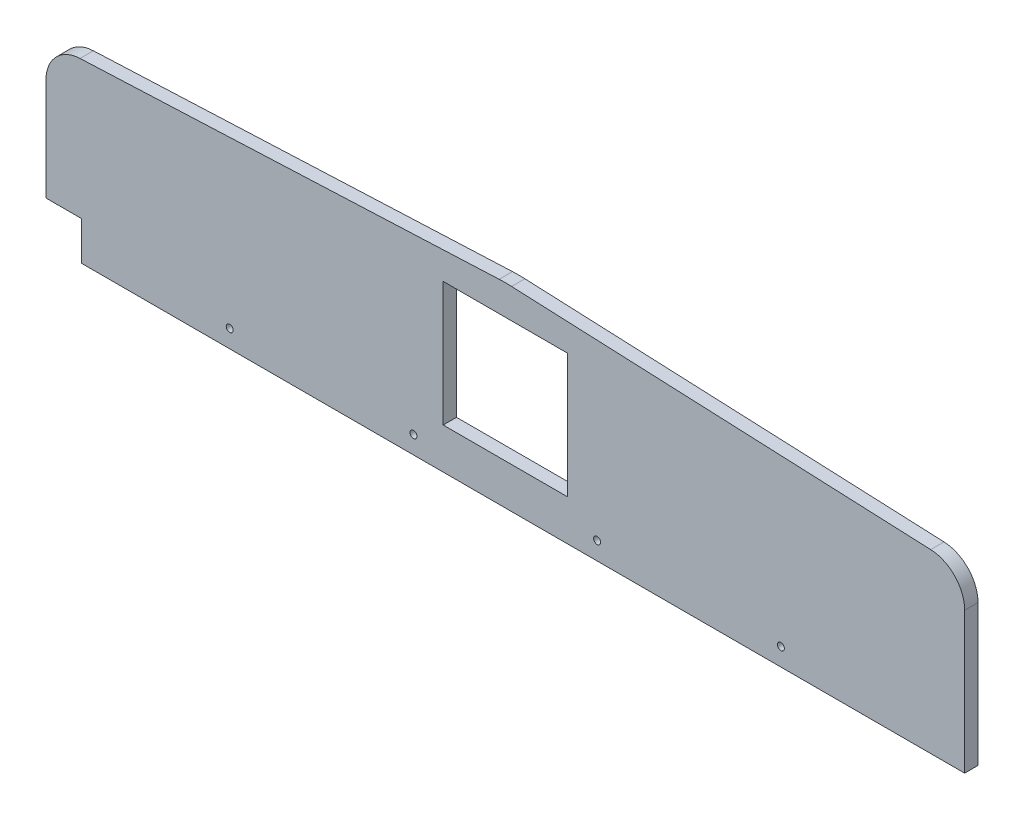
SolidWorks part; units mm, degrees
material "PC High Viscosity"
ref_plane "Front Plane" through (0, 0, 0) normal (0, 0, 1) x (1, 0, 0)
ref_plane "Top Plane" through (0, 0, 0) normal (0, 1, 0) x (1, 0, 0)
ref_plane "Right Plane" through (0, 0, 0) normal (1, 0, 0) x (0, 0, -1)
sketch "Sketch2" plane through (0, 0, 0) normal (0, 0, 1) x (1, 0, 0)
  line L0 (-328.3315, 55.6895) -> (-328.3315, 154.4895)
  line L1 (-328.3315, 154.4895) -> (0, 168.8465)
  line L2 (0, 168.8465) -> (328.2858, 154.4895)
  line L3 (328.2858, 154.4895) -> (328.2858, 55.6895)
  line L4 (328.2858, 55.6895) -> (328.2858, 29.2895)
  line L6 (328.2858, 29.2895) -> (-328.3315, 29.2895)
  line L7 (-328.3315, 29.2895) -> (-328.3315, 55.6895)
  dimension "D1" = 113.157
  dimension "D7" = 328.2858
  dimension "D8" = 98.8
  dimension "D9" = 26.4
extrude "Boss-Extrude1" add sketch "Sketch2" along normal mid plane 9.525
fillet "Fillet1" radius 25.4 2 edges at (328.2858, 154.4895, 0) (-328.3315, 154.4895, 0)
fillet "Fillet2" radius 101.6 1 edges at (0, 168.8465, 0)
sketch "Sketch3" plane through (0, 0, 4.7625) normal (0, 0, 1) x (1, 0, 0)
  line L0 (0, 0) -> (0, 192.0016) construction
  line L1 (-328.3315, 29.2895) -> (-302.9315, 29.2895)
  line L2 (-328.3315, 29.2895) -> (-328.3315, 56.9755)
  line L3 (-328.3315, 56.9755) -> (-302.9315, 56.9755)
  line L4 (-302.9315, 29.2895) -> (-302.9315, 56.9755)
  line L5 (0, 192.0016) -> (0, -60.0751) construction
  dimension "D1" = 25.4
  dimension "D2" = 27.686
extrude "Cut-Extrude1" cut sketch "Sketch3" against normal through all
sketch "Sketch5" plane through (0, 0, 4.7625) normal (0, 0, 1) x (1, 0, 0)
  line L1 (-44.45, 147.336) -> (44.45, 147.336)
  line L2 (-44.45, 147.336) -> (-44.45, 58.436)
  line L3 (-44.45, 58.436) -> (44.45, 58.436)
  line L4 (44.45, 147.336) -> (44.45, 58.436)
  line L5 (-44.45, 147.336) -> (44.45, 58.436) construction
  line L6 (-44.45, 58.436) -> (44.45, 147.336) construction
  point P0 (0, 102.886)
  dimension "D1" = 88.9
  dimension "D2" = 88.9
extrude "Cut-Extrude2" cut sketch "Sketch5" against normal through all
hole_wizard "Tap Drill for M6x1.0 Tap1" positions "Sketch7" profile "Sketch6" hole size "M6x1.0" standard "ANSI Metric" end condition through all
sketch "Sketch7" plane through (0, 0, 4.7625) normal (0, 0, 1) x (1, 0, 0)
  line L0 (-302.9315, 29.2895) -> (328.2858, 29.2895) construction
  line L1 (-328.3315, 130.1759) -> (-328.3315, 56.9755) construction
  point P0 (-197.0135, 41.9895)
  point P2 (-65.6955, 41.9895)
  point P4 (65.6225, 41.9895)
  point P6 (196.9405, 41.9895)
  dimension "D1" = 12.7
  dimension "D2" = 131.318
  dimension "D3" = 131.318
  dimension "D4" = 131.318
  dimension "D5" = 131.318
sketch "Sketch6" plane through (-197.0135, 41.9895, 4.7625) normal (1, 0, 0) x (0, -1, 0)
  line L0 (0, 0) -> (0, 9.525)
  line L1 (0, 9.525) -> (2.5, 9.525)
  line L2 (2.5, 9.525) -> (2.5, 0)
  line L5 (2.5, 0) -> (0, 0)
  line L11 (0, -6.35) -> (0, 107.95) construction
  dimension "Thru Hole Dia." = 5
  dimension "Thru Hole Depth" = 9.525
